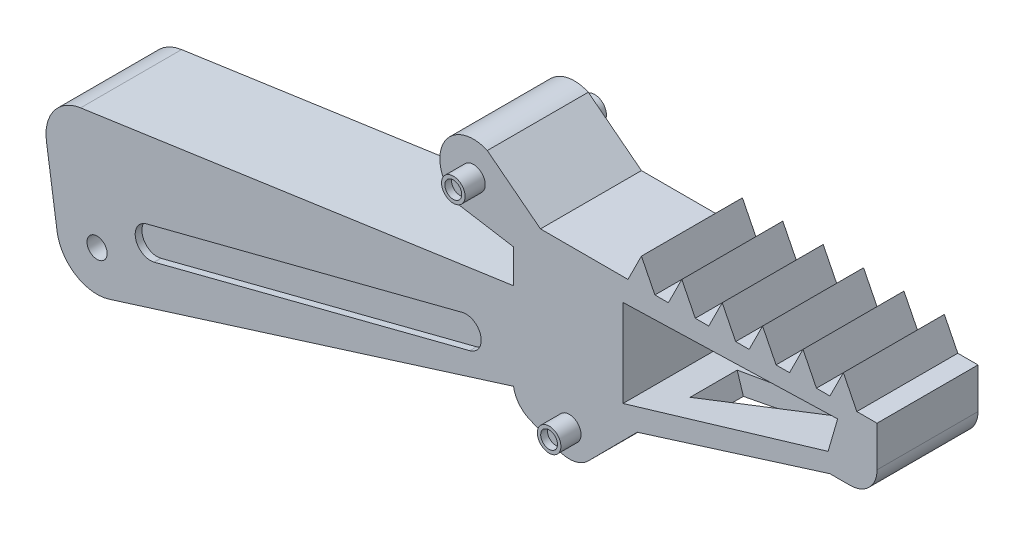
SolidWorks part; units mm, degrees
ref_plane "Front Plane" through (0, 0, 0) normal (1, 0, 0) x (0, 1, 0)
ref_plane "Top Plane" through (0, 0, 0) normal (0, 0, 1) x (0, 1, 0)
ref_plane "Right Plane" through (0, 0, 0) normal (0, 1, 0) x (-1, 0, 0)
sketch "Sketch1" plane through (0, 0, 0) normal (0, 0, 1) x (0, 1, 0)
  line L0 (0, 0) -> (-61.4425, 0) construction
  line L5 (-12.9366, 0) -> (-36.6831, -3.4789)
  line L6 (-36.6831, -3.4789) -> (-15.7438, -70.2737)
  line L8 (-2.8072, -70.2737) -> (-12.9366, 0)
  line L9 (-15.7438, -70.2737) -> (-17.8072, -70.2737)
  line L10 (-17.8072, -70.2737) -> (-21.697, -79.4862)
  line L11 (-21.697, -79.4862) -> (-12.467, -88.6408)
  line L12 (-12.467, -88.6408) -> (-3.493, -117.2671)
  line L13 (-3.493, -117.2671) -> (-3.493, -124.2671)
  line L14 (-3.493, -124.2671) -> (6.507, -124.2671)
  line L15 (6.507, -124.2671) -> (6.507, -74.2671)
  line L16 (-2.8072, -70.2737) -> (2.1928, -70.2737)
  line L17 (2.1928, -70.2737) -> (3.5187, -62.2648)
  line L18 (6.507, -74.2671) -> (12.6384, -66.3674)
  arc A0 (3.5187, -62.2648) -> (12.6384, -66.3674) centre (8.0785, -64.3161) cw
  dimension "D13" = 5
  dimension "D1" = 24
  dimension "D12" = 5
  dimension "D2" = 70
  dimension "D3" = 71
  dimension "D4" = 15
  dimension "D5" = 10
  dimension "D6" = 13
  dimension "D7" = 30
  dimension "D8" = 10
  dimension "D9" = 7
  dimension "D10" = 50
  dimension "D11" = 10
extrude "Boss-Extrude1" add sketch "Sketch1" along normal mid plane 15
fillet "Fillet1" radius 6 2 edges at (3.4789, -36.6831, 0) (0, -12.9366, 0)
fillet "Fillet2" radius 4 3 edges at (124.2671, -3.493, 0) (70.2737, -17.8072, 0) (79.4862, -21.697, 0)
sketch "Sketch2" plane through (0, 0, 7.5) normal (0, 0, 1) x (1, 0, 0)
  line L0 (124.2671, 6.507) -> (119.2671, 6.507)
  line L1 (124.2671, 6.507) -> (74.2671, 6.507) construction
  line L2 (119.2671, 6.507) -> (119.2671, 10.507) construction
  line L3 (121.2671, 6.507) -> (117.2671, 6.507)
  line L4 (117.2671, 6.507) -> (119.2671, 10.507)
  line L5 (119.2671, 10.507) -> (121.2671, 6.507)
  point P9 (119.2671, 6.507)
  line M6 (124.2671, 6.507) -> (74.2671, 6.507)
  dimension "D1" = 5
extrude "Boss-Extrude2" add sketch "Sketch2" against normal blind 15 contours L2 L0 L5 | L2 L4 M6 region at (119.9338, 7.8403, 7.5) region at (118.6005, 7.8403, 7.5)
pattern_linear "LPattern1" count 6 spacing 6 along (-1, 0, 0) of "Boss-Extrude2"
sketch "Sketch3" plane through (0, 0, 7.5) normal (0, 0, 1) x (1, 0, 0)
  line L6 (118.4148, 4.1346) -> (86.5328, 3.1767)
  line L7 (86.5328, 3.1767) -> (86.5328, -9.8208)
  line L8 (86.5328, -9.8208) -> (116.9952, -0.7511)
  line L9 (116.9952, -0.7511) -> (118.4148, 4.1346)
extrude "Cut-Extrude1" cut sketch "Sketch3" against normal blind 26
sketch "Sketch4" plane through (11.4902, -36.6528, 0) normal (0.2991, -0.9542, 0) x (0.9542, 0.2991, 0)
  line L0 (85.8528, 3.5) -> (85.8528, -3.5)
  line L1 (85.8528, -3.5) -> (106.8528, -0.5)
  line L2 (106.8528, -0.5) -> (106.8528, 0.5)
  line L5 (85.8528, 3.5) -> (106.8528, 0.5)
  line L6 (80.8528, 7.5) -> (110.8528, 7.5) construction
  line L7 (80.8528, 7.5) -> (80.8528, -7.5) construction
  line L8 (110.8528, 7.5) -> (110.8528, -7.5) construction
  line L9 (80.8528, -7.5) -> (110.8528, -7.5) construction
  dimension "D1" = 4
  dimension "D2" = 5
  dimension "D3" = 4
  dimension "D4" = 7
  dimension "D5" = 7
  dimension "D6" = 4
extrude "Cut-Extrude2" cut sketch "Sketch4" against normal blind 5
sketch "Sketch5" plane through (0, 0, 7.5) normal (0, 0, 1) x (1, 0, 0)
  circle A0 centre (8.396, -28.8538) radius 1.5
extrude "Cut-Extrude3" cut sketch "Sketch5" against normal through all
sketch "Sketch6" plane through (0, 0, 7.5) normal (0, 0, 1) x (1, 0, 0)
  circle A0 centre (78.5506, -16.96) radius 1.75
  circle A1 centre (64.3161, 8.0785) radius 1.75
extrude "Boss-Extrude3" add sketch "Sketch6" along normal blind 3
sketch "Sketch7" plane through (0, 0, 10.5) normal (0, 0, 1) x (1, 0, 0)
  circle A2 centre (78.5506, -16.96) radius 1.25
  circle A3 centre (78.5506, -16.96) radius 1.25
  dimension "D1" = 0.5
extrude "Cut-Extrude4" cut sketch "Sketch7" against normal blind 1
sketch "Sketch8" plane through (0, 0, 10.5) normal (0, 0, 1) x (1, 0, 0)
  circle A2 centre (64.3161, 8.0785) radius 1.25
  circle A3 centre (64.3161, 8.0785) radius 1.25
  dimension "D1" = 0.5
extrude "Cut-Extrude5" cut sketch "Sketch8" against normal blind 1
sketch "Sketch9" plane through (0, 0, 7.5) normal (0, 0, 1) x (1, 0, 0)
  line L0 (16.3147, -24.287) -> (63.2077, -12.2288) construction
  line L1 (15.7534, -22.104) -> (62.6463, -10.0458)
  line L2 (16.8761, -26.4701) -> (63.769, -14.4119)
  arc A0 (15.7534, -22.104) -> (16.8761, -26.4701) centre (16.3147, -24.287) ccw
  arc A1 (63.769, -14.4119) -> (62.6463, -10.0458) centre (63.2077, -12.2288) ccw
  point P2 (39.7612, -18.2579)
extrude "Cut-Extrude6" cut sketch "Sketch9" against normal blind 1
mirror "Mirror1" about plane through (0, 0, 0) normal (0, 0, 1) of "Cut-Extrude6", "Cut-Extrude5", "Cut-Extrude4", "Boss-Extrude3"
ref_point "Point1"
